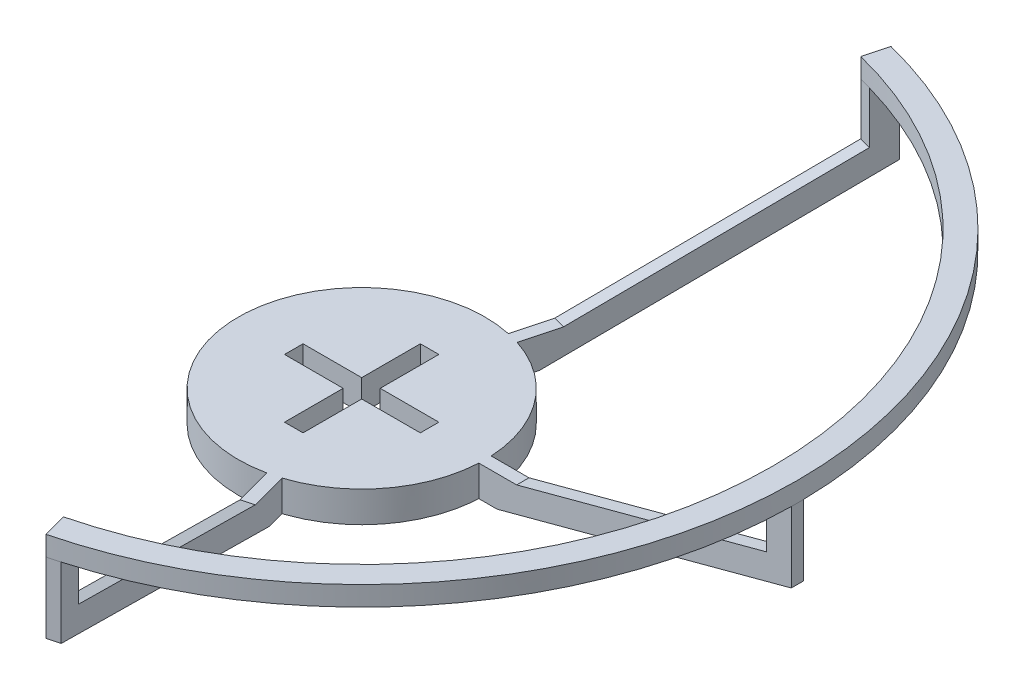
SolidWorks part; units mm, degrees
material "6061-T6 (SS)"
ref_plane "Front Plane" through (0, 0, 0) normal (0, 0, 1) x (1, 0, 0)
ref_plane "Top Plane" through (0, 0, 0) normal (0, 1, 0) x (1, 0, 0)
ref_plane "Right Plane" through (0, 0, 0) normal (1, 0, 0) x (0, 0, -1)
sketch "Sketch1" plane through (0, 0, 0) normal (0, 1, 0) x (1, 0, 0)
  circle A0 centre (0, 0) radius 20
  dimension "D1" = 40
extrude "Boss-Extrude1" add sketch "Sketch1" along normal blind 5
sketch "Sketch2" plane through (0, 0, 0) normal (0, 0, 1) x (1, 0, 0)
  line L0 (19.75, 5) -> (26.1, 5)
  line L1 (19.75, 0.0061) -> (19.75, 5)
  line L2 (26.1, 5) -> (66.582, 15.8471)
  line L3 (66.582, 15.8471) -> (66.582, 24.2078)
  line L4 (66.582, 24.2078) -> (70.582, 24.2078)
  line L5 (70.582, 24.2078) -> (70.582, 12.7778)
  line L6 (70.582, 12.7778) -> (22.9173, 0.0061)
  line L7 (22.9173, 0.0061) -> (19.75, 0.0061)
  point P0 (19.75, 0.0061)
  point P13 (33.9745, 0.7571)
  dimension "D1" = 6.35
  dimension "D2" = 41.91
  dimension "D3" = 4
  dimension "D4" = 11.43
  dimension "D5" = 4
  dimension "D6" = 15
  dimension "D7" = 19.75
extrude "Boss-Extrude2" add sketch "Sketch2" along normal blind 1 and the other way blind 1
pattern_circular "CirPattern1" count 2 every 75 about axis through (0, 5, 0) along (0, 1, 0) of "Boss-Extrude2"
pattern_circular "CirPattern3" count 2 every 75 about axis through (0, 0, 0) along (0, 1, 0) of "Boss-Extrude2" reverse direction yes
sketch "Sketch5" plane through (0, 5, 0) normal (0, 1, 0) x (1, 0, 0)
  line L1 (-11, -1.5) -> (-1.5, -1.5)
  line L2 (-11, -1.5) -> (-11, 1.5)
  line L3 (-11, 1.5) -> (-1.5, 1.5)
  line L4 (11, -1.5) -> (11, 1.5)
  line L5 (-11, -1.5) -> (11, 1.5) construction
  line L6 (-11, 1.5) -> (11, -1.5) construction
  line L7 (-1.5, -11) -> (1.5, -11)
  line L8 (-1.5, -11) -> (-1.5, -1.5)
  line L9 (-1.5, 11) -> (1.5, 11)
  line L10 (1.5, -11) -> (1.5, -1.5)
  line L11 (-1.5, -11) -> (1.5, 11) construction
  line L12 (-1.5, 11) -> (1.5, -11) construction
  line L15 (1.5, 1.5) -> (1.5, 11)
  line L16 (1.5, 1.5) -> (11, 1.5)
  line L18 (-1.5, 1.5) -> (-1.5, 11)
  line L21 (1.5, -1.5) -> (11, -1.5)
  point P2 (0, 0)
  point P8 (0, 0)
  dimension "D3" = 3
  dimension "D4" = 22
  dimension "D5" = 22
  dimension "D6" = 3
extrude "Cut-Extrude1" cut sketch "Sketch5" against normal up to next
sketch "Sketch7" plane through (0, 24.2078, 0) normal (0, 1, 0) x (1, 0, 0)
  line L0 (17.302, 68.4357) -> (16.2668, 64.572)
  line L1 (16.2668, -64.572) -> (17.302, -68.4357)
  arc A0 (17.302, -68.4357) -> (17.302, 68.4357) centre (0, 0) ccw
  arc A1 (16.2668, -64.572) -> (16.2668, 64.572) centre (0, 0) ccw
  point P7 (0, 0)
  point P12 (0, 0)
  point P13 (0, 0)
  point P14 (0, 0)
  point P15 (0, 0)
  point P16 (0, 0)
  point P17 (0, 0)
extrude "Boss-Extrude3" add sketch "Sketch7" along normal blind 3.175
